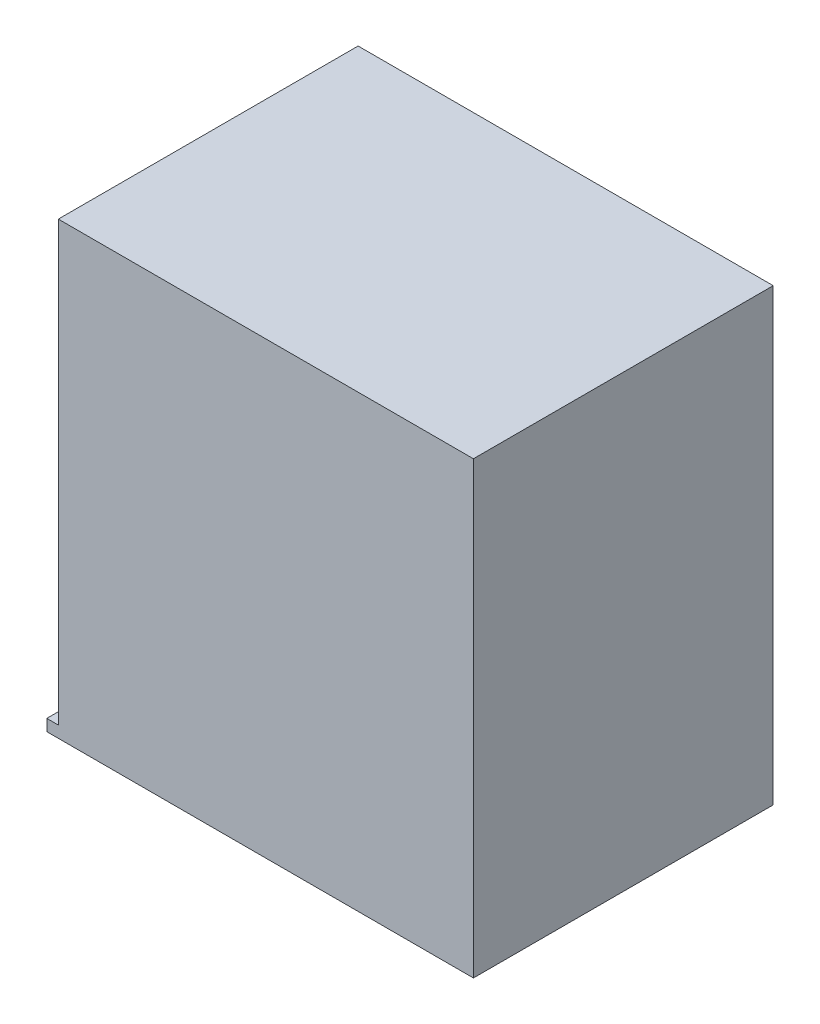
SolidWorks part; units mm, degrees
ref_plane "Ebene vorne" through (0, 0, 0) normal (0, 0, 1) x (1, 0, 0)
ref_plane "Ebene oben" through (0, 0, 0) normal (0, 1, 0) x (1, 0, 0)
ref_plane "Ebene rechts" through (0, 0, 0) normal (1, 0, 0) x (0, 0, -1)
sketch "Skizze1" plane through (0, 0, 0) normal (0, 0, 1) x (1, 0, 0)
  line L1 (-9.4467, 4.2096) -> (-79.4467, 4.2096)
  line L2 (-9.4467, 4.2096) -> (-9.4467, -69.7904)
  line L3 (-9.4467, -69.7904) -> (-79.4467, -69.7904)
  line L4 (-79.4467, 4.2096) -> (-79.4467, -69.7904)
  dimension "D1" = 70
  dimension "D2" = 74
extrude "Aufsatz-Linear austragen1" add sketch "Skizze1" along normal blind 2
sketch "Skizze2" plane through (-9.4467, 0, 0) normal (1, 0, 0) x (0, 0, -1)
  line L1 (-2, 4.2096) -> (50, 4.2096)
  line L2 (-2, 4.2096) -> (-2, -69.7904)
  line L3 (-2, -69.7904) -> (50, -69.7904)
  line L4 (50, 4.2096) -> (50, -69.7904)
  point P5 (-2, -69.7904)
  dimension "D1" = 52
extrude "Aufsatz-Linear austragen2" add sketch "Skizze2" along normal blind 2
sketch "Skizze3" plane through (0, -69.7904, 0) normal (0, -1, 0) x (1, 0, 0)
  line L1 (-7.4467, -50) -> (-81.4467, -50)
  line L2 (-7.4467, -50) -> (-7.4467, 2)
  line L3 (-7.4467, 2) -> (-81.4467, 2)
  line L4 (-81.4467, -50) -> (-81.4467, 2)
  point P6 (-79.4467, 2)
  point P7 (0, 0)
  dimension "D1" = 74
extrude "Aufsatz-Linear austragen3" add sketch "Skizze3" along normal blind 2
sketch "Skizze9" plane through (0, 4.2096, 0) normal (0, 1, 0) x (1, 0, 0)
  line L1 (-79.4467, -2) -> (-7.4467, -2)
  line L2 (-79.4467, -2) -> (-79.4467, 50)
  line L3 (-79.4467, 50) -> (-7.4467, 50)
  line L4 (-7.4467, -2) -> (-7.4467, 50)
extrude "Aufsatz-Linear austragen7" add sketch "Skizze9" along normal blind 2
